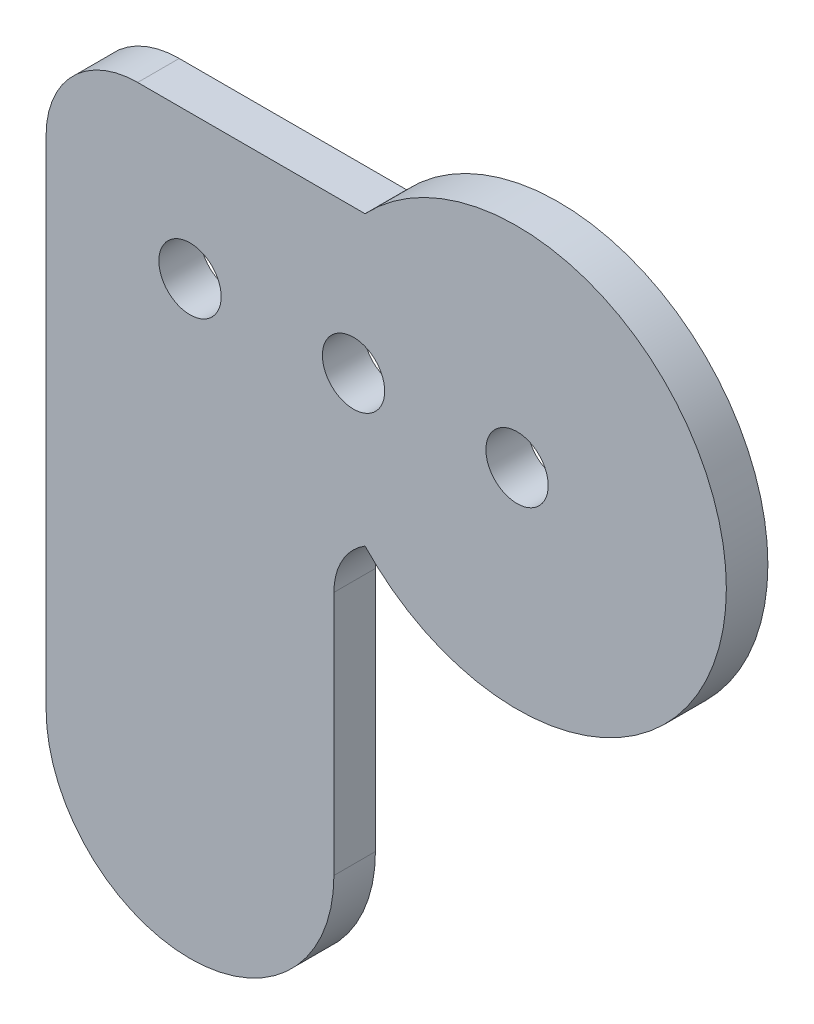
SolidWorks part; units mm, degrees
ref_plane "Front Plane" through (0, 0, 0) normal (0, 0, 1) x (1, 0, 0)
ref_plane "Top Plane" through (0, 0, 0) normal (0, 1, 0) x (1, 0, 0)
ref_plane "Right Plane" through (0, 0, 0) normal (1, 0, 0) x (0, 0, -1)
sketch "Sketch1" plane through (0, 0, 0) normal (0, 0, 1) x (1, 0, 0)
  line L0 (-11.619, 11) -> (-36, 11)
  line L1 (-36, 11) -> (-36, -34)
  line L2 (-14, -34) -> (-14, -11)
  line L3 (-14, -11) -> (-11.619, -11)
  arc A0 (-11.619, -11) -> (-11.619, 11) centre (0, 0) ccw
  arc A1 (-36, -34) -> (-14, -34) centre (-25, -34) ccw
  dimension "D1" = 32
  dimension "D7" = 25
  dimension "D2" = 11
  dimension "D3" = 11
  dimension "D4" = 34
  dimension "D6" = 22
extrude "Boss-Extrude1" add sketch "Sketch1" along normal blind 3.175
fillet "Fillet1" radius 7 1 edges at (-36, 11, 1.5875)
fillet "Fillet2" radius 5 1 edges at (-14, -11, 1.5875)
sketch "Sketch2" plane through (0, 0, 3.175) normal (0, 0, 1) x (1, 0, 0)
  circle A0 centre (0, 0) radius 2.3813
  dimension "D1" = 4.7625
extrude "Cut-Extrude1" cut sketch "Sketch2" against normal through all
pattern_linear "LPattern1" count 3 spacing 12.5 along (-1, 0, 0) of "Cut-Extrude1"
